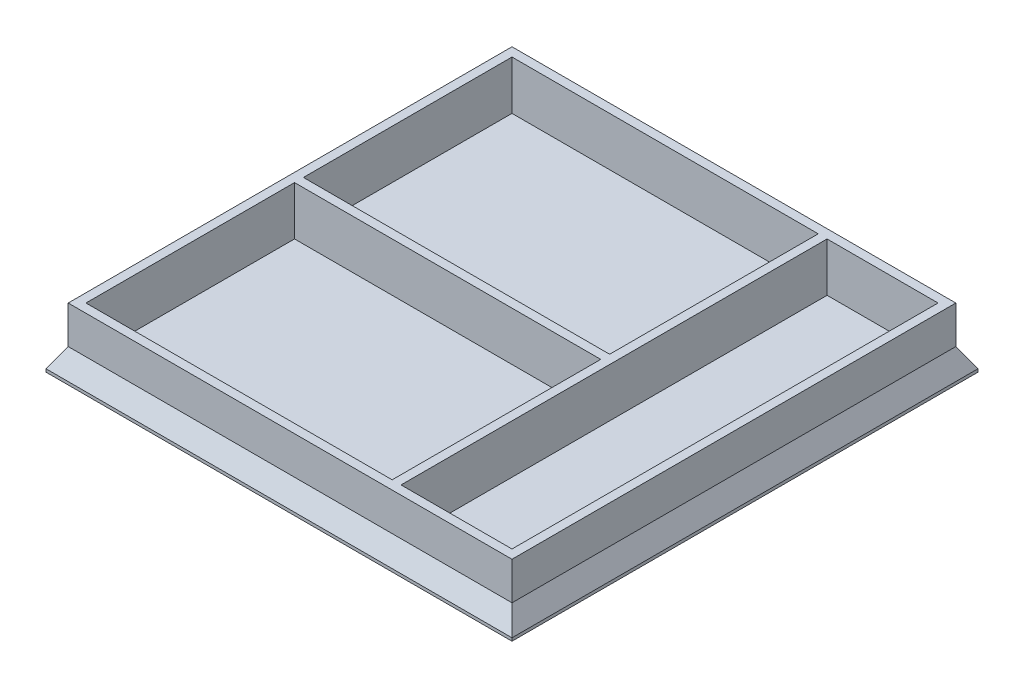
SolidWorks part; units mm, degrees
ref_plane "Přední rovina" through (0, 0, 0) normal (0, 0, 1) x (1, 0, 0)
ref_plane "Horní rovina" through (0, 0, 0) normal (0, 1, 0) x (1, 0, 0)
ref_plane "Pravá rovina" through (0, 0, 0) normal (1, 0, 0) x (0, 0, -1)
sketch "Skica1" plane through (0, 0, 0) normal (0, 1, 0) x (1, 0, 0)
  line L0 (-84, 84) -> (0, 0) construction
  line L1 (0, 0) -> (-84, 0)
  line L2 (0, 0) -> (0, 84)
  line L3 (0, 84) -> (-84, 84)
  line L4 (-84, 0) -> (-84, 84)
  line L5 (-84, 0) -> (0, 84) construction
  line L7 (-82, 82) -> (-2, 82)
  line L8 (-82, 82) -> (-82, 2)
  line L9 (-82, 2) -> (-2, 2)
  line L10 (-2, 82) -> (-2, 2)
  line L11 (-82, 82) -> (-2, 2) construction
  line L12 (-82, 2) -> (-2, 82) construction
  line L13 (-82, 42) -> (-2, 42) construction
  line L15 (-23.6, 80.4) -> (-3.6, 80.4)
  line L16 (-23.6, 80.4) -> (-23.6, 3.6)
  line L17 (-23.6, 3.6) -> (-3.6, 3.6)
  line L18 (-3.6, 80.4) -> (-3.6, 3.6)
  line L19 (-80.4, 80.4) -> (-25.2, 80.4)
  line L20 (-80.4, 80.4) -> (-80.4, 42.8)
  line L21 (-80.4, 42.8) -> (-25.2, 42.8)
  line L22 (-25.2, 80.4) -> (-25.2, 42.8)
  line L23 (-80.4, 41.2) -> (-25.2, 41.2)
  line L24 (-80.4, 41.2) -> (-80.4, 3.6)
  line L25 (-80.4, 3.6) -> (-25.2, 3.6)
  line L26 (-25.2, 41.2) -> (-25.2, 3.6)
  point P4 (-42, 42)
  dimension "D1" = 84
  dimension "D2" = 84
  dimension "D3" = 80
  dimension "D4" = 80
  dimension "D5" = 1.6
  dimension "D6" = 1.6
  dimension "D7" = 1.6
  dimension "D8" = 1.6
  dimension "D9" = 1.6
  dimension "D10" = 1.6
  dimension "D11" = 0.8
  dimension "D12" = 0.8
  dimension "D13" = 1.6
  dimension "D14" = 20
  dimension "D15" = 1.6
  dimension "D16" = 1.6
extrude "Přidat vysunutím1" add sketch "Skica1" along normal blind 2 contours L3 L4 L1 L2
extrude "Přidat vysunutím2" add sketch "Skica1<3>" along normal blind 10.8 contours L10 L7 L8 L9 L15 L18 L17 L16 L19 L22 L21 L20 L23 L26 L25 L24 region at (-40.3045, 0, -42)
sketch "Skica1<3>" plane through (0, 0, 0) normal (0, 1, 0) x (1, 0, 0) same geometry as "Skica1"
extrude "Přidat vysunutím3" add sketch "Skica1<4>" along normal blind 4 contours L4 L1 L2 L3 L7 L10 L9 L8 region at (-42, 0, -1.1879)
sketch "Skica1<4>" plane through (0, 0, 0) normal (0, 1, 0) x (1, 0, 0) same geometry as "Skica1"
chamfer "Zkosení2" distance 2 angle 60 4 edges at (-84, 4, -42) (-42, 4, -84) (0, 4, -42) (-42, 4, 0) first distance on face at (-42, 4, -42)
